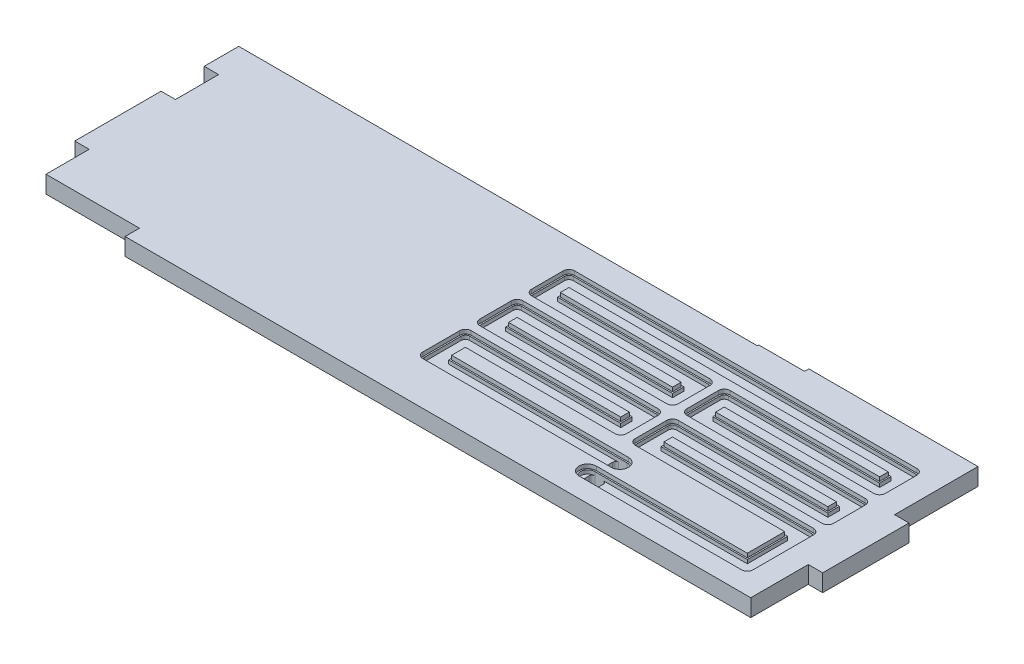
SolidWorks part; units mm, degrees
ref_plane "前视基准面" through (0, 0, 0) normal (0, 0, 1) x (1, 0, 0)
ref_plane "上视基准面" through (0, 0, 0) normal (0, 1, 0) x (1, 0, 0)
ref_plane "右视基准面" through (0, 0, 0) normal (1, 0, 0) x (0, 0, -1)
sketch "草图1" plane through (0, 0, 0) normal (0, 1, 0) x (1, 0, 0)
  line L0 (0, 0) -> (1803, 0)
  line L1 (1803, 0) -> (1803, 5)
  line L2 (1803, 5) -> (1962, 5)
  line L3 (1962, 5) -> (1962, 20)
  line L4 (1962, 20) -> (2550, 20)
  line L5 (2550, 20) -> (2550, -270)
  line L6 (2550, -270) -> (2600, -270)
  line L7 (2600, -270) -> (2600, -570)
  line L8 (2600, -570) -> (2550, -570)
  line L9 (2550, -570) -> (2550, -770)
  line L10 (2550, -770) -> (375, -770)
  line L11 (375, -770) -> (375, -720)
  line L12 (375, -720) -> (50, -720)
  line L13 (50, -720) -> (50, -570)
  line L14 (50, -570) -> (0, -570)
  line L15 (0, -570) -> (0, -270)
  line L16 (0, -270) -> (50, -270)
  line L17 (50, -270) -> (50, -120)
  line L18 (50, -120) -> (0, -120)
  line L19 (0, -120) -> (0, 0)
  line L20 (1885, -672) -> (2440, -672)
  line L21 (2440, -672) -> (2440, -482)
  line L22 (2440, -482) -> (1900, -482)
  line L23 (1900, -482) -> (1900, -392)
  line L24 (1900, -392) -> (2440, -392)
  line L25 (2440, -392) -> (2440, -302)
  line L26 (2440, -302) -> (1900, -302)
  line L27 (1900, -302) -> (1900, -212)
  line L28 (1900, -212) -> (2440, -212)
  line L29 (2440, -212) -> (2440, -122)
  line L30 (2440, -122) -> (1270, -122)
  line L31 (1270, -122) -> (1270, -212)
  line L32 (1270, -212) -> (1810, -212)
  line L33 (1810, -212) -> (1810, -302)
  line L34 (1810, -302) -> (1270, -302)
  line L35 (1270, -302) -> (1270, -392)
  line L36 (1270, -392) -> (1810, -392)
  line L37 (1810, -392) -> (1810, -482)
  line L38 (1810, -482) -> (1270, -482)
  line L39 (1270, -482) -> (1270, -590)
  line L40 (1270, -590) -> (1915, -590)
  line L41 (1885, -697) -> (2450, -697)
  line L42 (2465, -682) -> (2465, -472)
  line L43 (2450, -457) -> (1925, -457)
  line L44 (1925, -457) -> (1925, -417)
  line L45 (1925, -417) -> (2450, -417)
  line L46 (2465, -402) -> (2465, -292)
  line L47 (2450, -277) -> (1925, -277)
  line L48 (1925, -277) -> (1925, -237)
  line L49 (1925, -237) -> (2450, -237)
  line L50 (2465, -222) -> (2465, -112)
  line L51 (2450, -97) -> (1260, -97)
  line L52 (1245, -112) -> (1245, -222)
  line L53 (1260, -237) -> (1785, -237)
  line L54 (1785, -237) -> (1785, -277)
  line L55 (1785, -277) -> (1260, -277)
  line L56 (1245, -292) -> (1245, -402)
  line L57 (1260, -417) -> (1785, -417)
  line L58 (1785, -417) -> (1785, -457)
  line L59 (1785, -457) -> (1260, -457)
  line L60 (1245, -472) -> (1245, -600)
  line L61 (1260, -615) -> (1915, -615)
  line L62 (1885, -647) -> (2415, -647)
  line L63 (2415, -647) -> (2415, -507)
  line L64 (2415, -507) -> (1890, -507)
  line L65 (1875, -492) -> (1875, -382)
  line L66 (1890, -367) -> (2415, -367)
  line L67 (2415, -367) -> (2415, -327)
  line L68 (2415, -327) -> (1890, -327)
  line L69 (1875, -312) -> (1875, -202)
  line L70 (1890, -187) -> (2415, -187)
  line L71 (2415, -187) -> (2415, -147)
  line L72 (2415, -147) -> (1295, -147)
  line L73 (1295, -147) -> (1295, -187)
  line L74 (1295, -187) -> (1820, -187)
  line L75 (1835, -202) -> (1835, -312)
  line L76 (1820, -327) -> (1295, -327)
  line L77 (1295, -327) -> (1295, -367)
  line L78 (1295, -367) -> (1820, -367)
  line L79 (1835, -382) -> (1835, -492)
  line L80 (1820, -507) -> (1295, -507)
  line L81 (1295, -507) -> (1295, -565)
  line L82 (1295, -565) -> (1915, -565)
  line L83 (1295, -187) -> (1835, -187) construction
  line L84 (1835, -187) -> (1835, -327) construction
  line L85 (1835, -327) -> (1295, -327) construction
  line L86 (1295, -367) -> (1835, -367) construction
  line L87 (1835, -367) -> (1835, -507) construction
  line L88 (1835, -507) -> (1295, -507) construction
  line L89 (1245, -457) -> (1245, -615) construction
  line L90 (1245, -615) -> (1915, -615) construction
  line L91 (1785, -457) -> (1245, -457) construction
  line L92 (1245, -277) -> (1245, -417) construction
  line L93 (1245, -417) -> (1785, -417) construction
  line L94 (1785, -277) -> (1245, -277) construction
  line L95 (1245, -97) -> (1245, -237) construction
  line L96 (1245, -237) -> (1785, -237) construction
  line L97 (2465, -97) -> (1245, -97) construction
  line L98 (2465, -237) -> (2465, -97) construction
  line L99 (1925, -237) -> (2465, -237) construction
  line L100 (2465, -417) -> (2465, -277) construction
  line L101 (2465, -277) -> (1925, -277) construction
  line L102 (1925, -417) -> (2465, -417) construction
  line L103 (1875, -327) -> (1875, -187) construction
  line L104 (1875, -187) -> (2415, -187) construction
  line L105 (2415, -327) -> (1875, -327) construction
  line L106 (1875, -507) -> (1875, -367) construction
  line L107 (1875, -367) -> (2415, -367) construction
  line L108 (2415, -507) -> (1875, -507) construction
  line L109 (2465, -697) -> (2465, -457) construction
  line L110 (2465, -457) -> (1925, -457) construction
  line L111 (1885, -697) -> (2465, -697) construction
  line L112 (1885, -702) -> (2450, -702)
  line L113 (2470, -682) -> (2470, -472)
  line L114 (2450, -452) -> (1930, -452)
  line L115 (1930, -452) -> (1930, -422)
  line L116 (1930, -422) -> (2450, -422)
  line L117 (2470, -402) -> (2470, -292)
  line L118 (2450, -272) -> (1930, -272)
  line L119 (1930, -272) -> (1930, -242)
  line L120 (1930, -242) -> (2450, -242)
  line L121 (2470, -222) -> (2470, -112)
  line L122 (2450, -92) -> (1260, -92)
  line L123 (1240, -112) -> (1240, -222)
  line L124 (1260, -242) -> (1780, -242)
  line L125 (1780, -242) -> (1780, -272)
  line L126 (1780, -272) -> (1260, -272)
  line L127 (1240, -292) -> (1240, -402)
  line L128 (1260, -422) -> (1780, -422)
  line L129 (1780, -422) -> (1780, -452)
  line L130 (1780, -452) -> (1260, -452)
  line L131 (1240, -472) -> (1240, -600)
  line L132 (1260, -620) -> (1915, -620)
  line L133 (1300, -560) -> (1915, -560)
  line L134 (1300, -512) -> (1300, -560)
  line L135 (1820, -512) -> (1300, -512)
  line L136 (1840, -382) -> (1840, -492)
  line L137 (1300, -362) -> (1820, -362)
  line L138 (1300, -332) -> (1300, -362)
  line L139 (1820, -332) -> (1300, -332)
  line L140 (1840, -202) -> (1840, -312)
  line L141 (1300, -182) -> (1820, -182)
  line L142 (1300, -152) -> (1300, -182)
  line L143 (2410, -152) -> (1300, -152)
  line L144 (2410, -182) -> (2410, -152)
  line L145 (1890, -182) -> (2410, -182)
  line L146 (1870, -312) -> (1870, -202)
  line L147 (2410, -332) -> (1890, -332)
  line L148 (2410, -362) -> (2410, -332)
  line L149 (1890, -362) -> (2410, -362)
  line L150 (1870, -492) -> (1870, -382)
  line L151 (2410, -512) -> (1890, -512)
  line L152 (2410, -642) -> (2410, -512)
  line L153 (1885, -642) -> (2410, -642)
  line L155 (1907.5, -607.5) -> (1892.5, -607.5)
  line L156 (1917.5, -597.5) -> (1917.5, -582.5)
  line L157 (1907.5, -572.5) -> (1892.5, -572.5)
  line L158 (1882.5, -597.5) -> (1882.5, -582.5)
  line L159 (1917.5, -607.5) -> (1882.5, -572.5) construction
  line L160 (1917.5, -572.5) -> (1882.5, -607.5) construction
  line L165 (1915, -615) -> (1885, -615)
  line L166 (1925, -605) -> (1925, -575)
  line L167 (1915, -565) -> (1885, -565)
  line L168 (1875, -605) -> (1875, -575)
  line L169 (1925, -615) -> (1875, -565) construction
  line L170 (1925, -565) -> (1875, -615) construction
  arc A0 (1885, -697) -> (1885, -647) centre (1885, -672) cw
  arc A1 (1915, -615) -> (1915, -565) centre (1915, -590) ccw
  arc A2 (1820, -187) -> (1835, -202) centre (1820, -202) cw
  arc A3 (1835, -312) -> (1820, -327) centre (1820, -312) cw
  arc A4 (1820, -367) -> (1835, -382) centre (1820, -382) cw
  arc A5 (1835, -492) -> (1820, -507) centre (1820, -492) cw
  arc A6 (1245, -600) -> (1260, -615) centre (1260, -600) ccw
  arc A7 (1260, -457) -> (1245, -472) centre (1260, -472) ccw
  arc A8 (1245, -402) -> (1260, -417) centre (1260, -402) ccw
  arc A9 (1260, -277) -> (1245, -292) centre (1260, -292) ccw
  arc A10 (1245, -222) -> (1260, -237) centre (1260, -222) ccw
  arc A11 (1260, -97) -> (1245, -112) centre (1260, -112) ccw
  arc A12 (2465, -112) -> (2450, -97) centre (2450, -112) ccw
  arc A13 (2450, -237) -> (2465, -222) centre (2450, -222) ccw
  arc A14 (2465, -292) -> (2450, -277) centre (2450, -292) ccw
  arc A15 (2450, -417) -> (2465, -402) centre (2450, -402) ccw
  arc A16 (1875, -202) -> (1890, -187) centre (1890, -202) cw
  arc A17 (1890, -327) -> (1875, -312) centre (1890, -312) cw
  arc A18 (1875, -382) -> (1890, -367) centre (1890, -382) cw
  arc A19 (1890, -507) -> (1875, -492) centre (1890, -492) cw
  arc A20 (2465, -472) -> (2450, -457) centre (2450, -472) ccw
  arc A21 (2450, -697) -> (2465, -682) centre (2450, -682) ccw
  arc A22 (2450, -702) -> (2470, -682) centre (2450, -682) ccw
  arc A23 (2470, -472) -> (2450, -452) centre (2450, -472) ccw
  arc A24 (2450, -422) -> (2470, -402) centre (2450, -402) ccw
  arc A25 (2470, -292) -> (2450, -272) centre (2450, -292) ccw
  arc A26 (2450, -242) -> (2470, -222) centre (2450, -222) ccw
  arc A27 (2470, -112) -> (2450, -92) centre (2450, -112) ccw
  arc A28 (1260, -92) -> (1240, -112) centre (1260, -112) ccw
  arc A29 (1240, -222) -> (1260, -242) centre (1260, -222) ccw
  arc A30 (1260, -272) -> (1240, -292) centre (1260, -292) ccw
  arc A31 (1240, -402) -> (1260, -422) centre (1260, -402) ccw
  arc A32 (1260, -452) -> (1240, -472) centre (1260, -472) ccw
  arc A33 (1240, -600) -> (1260, -620) centre (1260, -600) ccw
  arc A34 (1915, -620) -> (1915, -560) centre (1915, -590) ccw
  arc A35 (1840, -492) -> (1820, -512) centre (1820, -492) cw
  arc A36 (1820, -362) -> (1840, -382) centre (1820, -382) cw
  arc A37 (1840, -312) -> (1820, -332) centre (1820, -312) cw
  arc A38 (1820, -182) -> (1840, -202) centre (1820, -202) cw
  arc A39 (1870, -202) -> (1890, -182) centre (1890, -202) cw
  arc A40 (1890, -332) -> (1870, -312) centre (1890, -312) cw
  arc A41 (1870, -382) -> (1890, -362) centre (1890, -382) cw
  arc A42 (1890, -512) -> (1870, -492) centre (1890, -492) cw
  arc A43 (1885, -702) -> (1885, -642) centre (1885, -672) cw
  arc A44 (1892.5, -607.5) -> (1882.5, -597.5) centre (1892.5, -597.5) cw
  arc A45 (1907.5, -607.5) -> (1917.5, -597.5) centre (1907.5, -597.5) ccw
  arc A46 (1917.5, -582.5) -> (1907.5, -572.5) centre (1907.5, -582.5) ccw
  arc A47 (1892.5, -572.5) -> (1882.5, -582.5) centre (1892.5, -582.5) ccw
  arc A52 (1925, -575) -> (1915, -565) centre (1915, -575) ccw
  arc A53 (1915, -615) -> (1925, -605) centre (1915, -605) ccw
  arc A54 (1885, -615) -> (1875, -605) centre (1885, -605) cw
  arc A55 (1885, -565) -> (1875, -575) centre (1885, -575) ccw
  point P234 (1900, -590)
  point P241 (1945, -590)
  point P254 (1900, -590)
  point P268 (0, 0)
  point P269 (0, 0)
  point P270 (0, 0)
  point P271 (1882.8908, -672)
  point P272 (1855, -672)
  dimension "D30" = 20
  dimension "D36" = 10
  dimension "D38" = 50
  dimension "D37" = 50
  dimension "D39" = 10
  dimension "D1" = 2600
  dimension "D2" = 790
  dimension "D3" = 200
  dimension "D4" = 300
  dimension "D5" = 15
  dimension "D6" = 5
  dimension "D7" = 375
  dimension "D8" = 50
  dimension "D9" = 50
  dimension "D10" = 150
  dimension "D11" = 300
  dimension "D12" = 150
  dimension "D13" = 50
  dimension "D14" = 588
  dimension "D15" = 159
  dimension "D16" = 98
  dimension "D17" = 190
  dimension "D18" = 90
  dimension "D19" = 90
  dimension "D20" = 90
  dimension "D21" = 90
  dimension "D22" = 108
  dimension "D23" = 110
  dimension "D24" = 540
  dimension "D25" = 1170
  dimension "D26" = 540
  dimension "D27" = 555
  dimension "D32" = 650
  dimension "D33" = 35
  dimension "D34" = 35
  dimension "D35" = 45
  dimension "D40" = 1230
  dimension "D28" = 25
  dimension "D29" = 25
  dimension "D31" = 5
extrude "凸台-拉伸1" add sketch "草图1" against normal blind 60 contours L0 L1 L2 L3 L4 L5 L6 L7 L8 L9 L10 L11 L12 L13 L14 L15 L16 L17 L18 L19
extrude "切除-拉伸2" cut sketch "草图1<4>" against normal blind 27 contours L41 A21 L42 A20 L43 L44 L45 A15 L46 A14 L47 L48 L49 A13 L50 A12 L51 A11 L52 A10 L53 L54 L55 A9 L56 A8 L57 L58 L59 A7 L60 A6 L61 A1 L82 L81 L80 A5 L79 A4 L78 L77 L76 A3 L75 A2 L74 L73 L72 L71 L70 A16 L69 A17 L68 L67 L66 A18 L65 A19 L64 L63 L62 A0
sketch "草图1<4>" plane through (0, 0, 0) normal (0, 1, 0) x (1, 0, 0) same geometry as "草图1"
extrude "切除-拉伸3" cut sketch "草图1<5>" against normal blind 14 contours L112 A22 L113 A23 L114 L115 L116 A24 L117 A25 L118 L119 L120 A26 L121 A27 L122 A28 L123 A29 L124 L125 L126 A30 L127 A31 L128 L129 L130 A32 L131 A33 L132 A34 L133 L134 L135 A35 L136 A36 L137 L138 L139 A37 L140 A38 L141 L142 L143 L144 L145 A39 L146 A40 L147 L148 L149 A41 L150 A42 L151 L152 L153 A43
sketch "草图1<5>" plane through (0, 0, 0) normal (0, 1, 0) x (1, 0, 0) same geometry as "草图1"
sketch "草图3" plane through (0, 0, 0) normal (0, 1, 0) x (1, 0, 0)
  line L0 (1885, -672) -> (2440, -672) construction
  line L1 (1907.5, -689.5) -> (1892.5, -689.5)
  line L2 (1917.5, -679.5) -> (1917.5, -664.5)
  line L3 (1907.5, -654.5) -> (1892.5, -654.5)
  line L4 (1882.5, -679.5) -> (1882.5, -664.5)
  line L5 (1917.5, -689.5) -> (1882.5, -654.5) construction
  line L6 (1917.5, -654.5) -> (1882.5, -689.5) construction
  line L7 (2550, -570) -> (2550, -770) construction
  line L13 (1915, -697) -> (1885, -697)
  line L14 (1925, -687) -> (1925, -657)
  line L15 (1915, -647) -> (1885, -647)
  line L16 (1875, -687) -> (1875, -657)
  line L17 (1925, -697) -> (1875, -647) construction
  line L18 (1925, -647) -> (1875, -697) construction
  arc A0 (1917.5, -664.5) -> (1907.5, -654.5) centre (1907.5, -664.5) ccw
  arc A1 (1892.5, -689.5) -> (1882.5, -679.5) centre (1892.5, -679.5) cw
  arc A2 (1917.5, -679.5) -> (1907.5, -689.5) centre (1907.5, -679.5) cw
  arc A3 (1882.5, -664.5) -> (1892.5, -654.5) centre (1892.5, -664.5) cw
  arc A8 (1925, -657) -> (1915, -647) centre (1915, -657) ccw
  arc A9 (1915, -697) -> (1925, -687) centre (1915, -687) ccw
  arc A10 (1885, -697) -> (1875, -687) centre (1885, -687) cw
  arc A11 (1885, -647) -> (1875, -657) centre (1885, -657) ccw
  arc A12 (1885, -642) -> (1885, -702) centre (1885, -672) ccw construction
  arc A13 (1885, -642) -> (1885, -702) centre (1885, -672) ccw
  point P0 (1900, -672)
  point P21 (1900, -672)
  point P41 (0, 0)
  dimension "D4" = 10
  dimension "D7" = 10
  dimension "D1" = 650
  dimension "D2" = 35
  dimension "D3" = 35
  dimension "D5" = 50
  dimension "D6" = 50
extrude "切除-拉伸4" cut sketch "草图3" against normal blind 55 contours L1 A1 L4 A3 L3 A0 L2 A2
extrude "切除-拉伸5" cut sketch "草图3<3>" against normal blind 60 contours L3 A3 L4 A1 L1 A2 L2 A0
sketch "草图3<3>" plane through (0, 0, 0) normal (0, 1, 0) x (1, 0, 0) same geometry as "草图3"
extrude "切除-拉伸6" cut sketch "草图1<6>" against normal blind 60 contours L158 A47 L157 A46 L156 A45 L155 A44
sketch "草图1<6>" plane through (0, 0, 0) normal (0, 1, 0) x (1, 0, 0) same geometry as "草图1"
extrude "切除-拉伸7" cut sketch "草图1<7>" against normal blind 55 contours A52 L167 A55 L168 A54 L165 A53 L166
sketch "草图1<7>" plane through (0, 0, 0) normal (0, 1, 0) x (1, 0, 0) same geometry as "草图1"
extrude "切除-拉伸8" cut sketch "草图3<4>" against normal blind 55 contours A11 L16 A10 L13 A9 L14 A8 L15
sketch "草图3<4>" plane through (0, 0, 0) normal (0, 1, 0) x (1, 0, 0) same geometry as "草图3"
